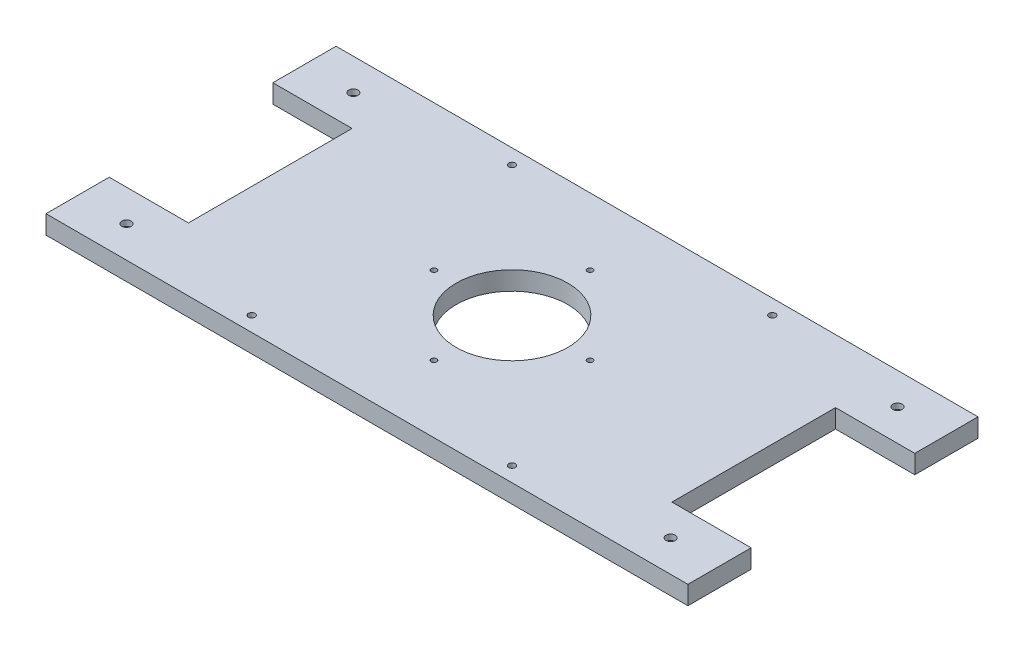
SolidWorks part; units mm, degrees
ref_plane "前视基准面" through (0, 0, 0) normal (0, 0, 1) x (1, 0, 0)
ref_plane "上视基准面" through (0, 0, 0) normal (0, 1, 0) x (1, 0, 0)
ref_plane "右视基准面" through (0, 0, 0) normal (1, 0, 0) x (0, 0, -1)
other "Configuration Table"
sketch "草图1" plane through (0, 0, 0) normal (0, 1, 0) x (1, 0, 0)
  line L0 (-73.15, 30.5) -> (73.15, -30.5) construction
  line L1 (-86.3, -39) -> (86.3, -39)
  line L2 (-86.3, -39) -> (-86.3, 39)
  line L3 (-86.3, 39) -> (86.3, 39)
  line L4 (86.3, -39) -> (86.3, 39)
  line L5 (-86.3, -39) -> (86.3, 39) construction
  line L6 (-86.3, 39) -> (86.3, -39) construction
  circle A0 centre (-73.15, 30.5) radius 2
  circle A1 centre (-73.15, 30.5) radius 1.25
  circle A2 centre (-73.15, -30.5) radius 2
  circle A3 centre (-73.15, -30.5) radius 1.25
  circle A4 centre (73.15, 30.5) radius 2
  circle A5 centre (73.15, 30.5) radius 1.25
  circle A6 centre (73.15, -30.5) radius 2
  circle A7 centre (73.15, -30.5) radius 1.25
  point P0 (0, 0)
  dimension "D3" = 2.5
  dimension "D4" = 4
  dimension "D1" = 61
  dimension "D2" = 146.3
  dimension "D5" = 13.15
  dimension "D6" = 8.5
extrude "凸台-拉伸1" add sketch "草图1" along normal blind 5 contours L3 L4 L1 L2 | A1 | A5 | A7 | A3
sketch "草图2" plane through (0, 5, 0) normal (0, 1, 0) x (1, 0, 0)
  line L0 (-86.3, -39) -> (-86.3, 39) construction
  line L1 (-86.3, 39) -> (-65, 39)
  line L2 (-86.3, 39) -> (-86.3, 22)
  line L3 (-86.3, 22) -> (-65, 22)
  line L4 (-65, 39) -> (-65, 22)
  line L5 (-86.3, -39) -> (86.3, -39) construction
  line L6 (-86.3, -39) -> (-65, -39)
  line L7 (-86.3, -39) -> (-86.3, -22)
  line L8 (-86.3, -22) -> (-65, -22)
  line L9 (-65, -39) -> (-65, -22)
  line L10 (-86.3, 39) -> (86.3, 39) construction
  line L11 (86.3, 39) -> (65, 39)
  line L12 (86.3, 39) -> (86.3, 22)
  line L13 (86.3, 22) -> (65, 22)
  line L14 (65, 39) -> (65, 22)
  line L15 (86.3, -39) -> (86.3, 39) construction
  line L16 (86.3, -39) -> (65, -39)
  line L17 (86.3, -39) -> (86.3, -22)
  line L18 (86.3, -22) -> (65, -22)
  line L19 (65, -39) -> (65, -22)
  line L20 (-65, 22) -> (-65, -22)
  line L21 (65, -22) -> (65, 22)
  circle A0 centre (-73.15, 30.5) radius 1.25 construction
  line M17 (-86.3, 39) -> (-86.3, -39)
  line M19 (86.3, -39) -> (86.3, 39)
  dimension "D1" = 8.5
  dimension "D2" = 8.15
extrude "切除-拉伸1" cut sketch "草图2" against normal through all contours L20 L3 L8 M17 | L21 L18 L13 M19 region at (-75.65, 5, 0) region at (75.65, 5, 0)
extrude "切除-拉伸2" cut sketch "草图1<3>" along normal offset from surface (3.5 mm away) 1.5 contours A0 | A2 | A6 | A4 up to face at (0, 5, 0)
sketch "草图1<3>" plane through (0, 0, 0) normal (0, 1, 0) x (1, 0, 0) same geometry as "草图1"
sketch "草图3" plane through (0, 5, 0) normal (0, 1, 0) x (1, 0, 0)
  line L0 (-35, 35) -> (35, 35) construction
  line L1 (35, 35) -> (35, -35) construction
  line L2 (-35, -35) -> (35, -35) construction
  circle A0 centre (-35, 35) radius 0.9
  circle A1 centre (35, 35) radius 0.9
  circle A2 centre (-35, -35) radius 0.9
  circle A3 centre (35, -35) radius 0.9
  point P8 (35, 0)
  point P9 (0, 35)
  dimension "D1" = 1.8
  dimension "D2" = 70
extrude "切除-拉伸3" cut sketch "草图3" against normal through all
sketch "草图4" plane through (0, 0, 0) normal (0, -1, 0) x (1, 0, 0)
  circle A0 centre (0, 0) radius 15
  dimension "D1" = 30
extrude "切除-拉伸4" cut sketch "草图4" against normal through all
sketch "草图5" plane through (0, 5, 0) normal (0, 1, 0) x (1, 0, 0)
  line L0 (-21, 0) -> (0, 0) construction
  line L1 (0, 0) -> (0, -21) construction
  line L2 (0, 0) -> (21, 0) construction
  line L3 (0, 21) -> (0, 0) construction
  circle A0 centre (0, 21) radius 0.75
  circle A1 centre (21, 0) radius 0.75
  circle A2 centre (-21, 0) radius 0.75
  circle A3 centre (0, -21) radius 0.75
  dimension "D1" = 1.5
  dimension "D2" = 21
extrude "切除-拉伸5" cut sketch "草图5" against normal through all
